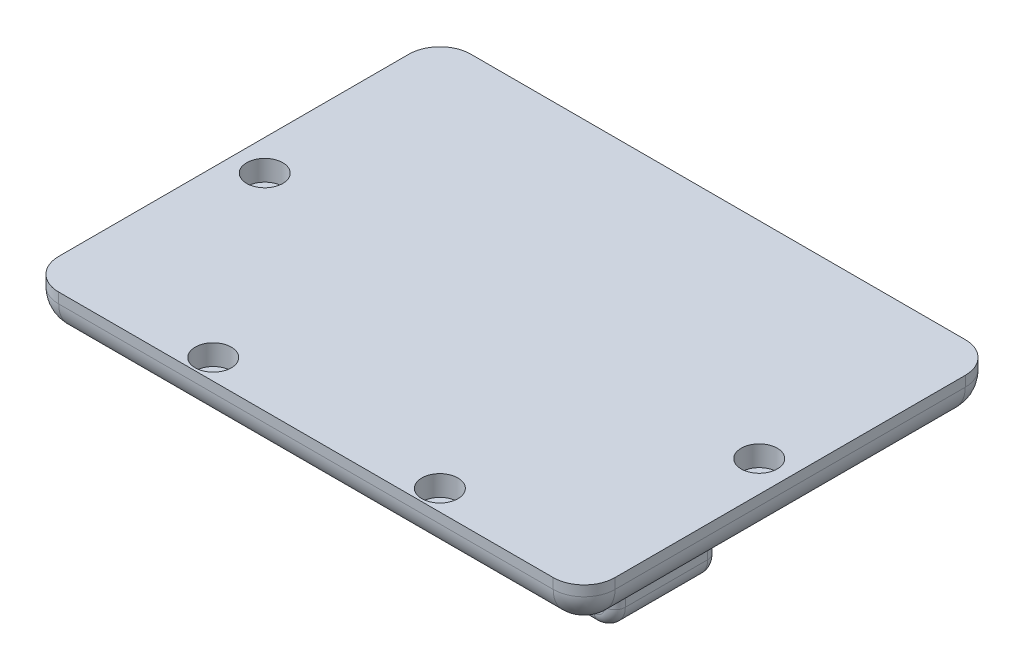
SolidWorks part; units mm, degrees
ref_plane "Plan de face" through (0, 0, 0) normal (0, 0, 1) x (1, 0, 0)
ref_plane "Plan de dessus" through (0, 0, 0) normal (0, 1, 0) x (1, 0, 0)
ref_plane "Plan de droite" through (0, 0, 0) normal (1, 0, 0) x (0, 0, -1)
sketch "Esquisse1" plane through (0, 0, 0) normal (0, 1, 0) x (1, 0, 0)
  line L1 (-27, 20) -> (27, 20)
  line L2 (-27, 20) -> (-27, -20)
  line L3 (-27, -20) -> (27, -20)
  line L4 (27, 20) -> (27, -20)
  line L5 (-27, 20) -> (27, -20) construction
  line L6 (-27, -20) -> (27, 20) construction
  point P0 (0, 0)
  dimension "D1" = 40
  dimension "D2" = 54
extrude "Boss.-Extru.1" add sketch "Esquisse1" along normal blind 4
sketch "Esquisse2" plane through (0, 4, 0) normal (0, 1, 0) x (1, 0, 0)
  line L0 (-27, 20) -> (-27, -20) construction
  line L1 (-27, -20) -> (27, -20) construction
  line L2 (27, -20) -> (27, 20) construction
  circle A0 centre (-24, 0) radius 1.75
  circle A1 centre (-11, -18) radius 1.75
  circle A2 centre (11, -18) radius 1.75
  circle A3 centre (24, 0) radius 1.75
  dimension "D3" = 3.5
  dimension "D6" = 3.5
  dimension "D7" = 3.5
  dimension "D12" = 3.5
  dimension "D1" = 3
  dimension "D2" = 20
  dimension "D4" = 2
  dimension "D5" = 16
  dimension "D8" = 2
  dimension "D9" = 16
  dimension "D10" = 3
  dimension "D11" = 20
fillet "Congé1" radius 3 8 edges at (27, 2, 20) (0, 0, 20) (-27, 2, 20) (-27, 0, 0) (-27, 2, -20) (27, 0, 0) (0, 0, -20) (27, 2, -20)
sketch "Esquisse3" plane through (0, 0, 0) normal (0, -1, 0) x (1, 0, 0)
  line L1 (15, -5) -> (-15, -5)
  line L2 (15, -5) -> (15, 5)
  line L3 (15, 5) -> (-15, 5)
  line L4 (-15, -5) -> (-15, 5)
  line L5 (15, -5) -> (-15, 5) construction
  line L6 (15, 5) -> (-15, -5) construction
  point P0 (0, 0)
  dimension "D1" = 30
  dimension "D2" = 10
extrude "Boss.-Extru.3" add sketch "Esquisse3" along normal blind 13
fillet "Congé4" radius 2 4 edges at (-15, 0, 0) (0, 0, 5) (15, 0, 0) (0, 0, -5)
sketch "Esquisse4" plane through (0, 0, -5) normal (0, 0, -1) x (-1, 0, 0)
  line L0 (-15, -13) -> (-15, -2) construction
  line L1 (-12, -4) -> (12, -4)
  line L2 (-12, -4) -> (-12, -10)
  line L3 (-12, -10) -> (12, -10)
  line L4 (12, -4) -> (12, -10)
  line L5 (-12, -4) -> (12, -10) construction
  line L6 (-12, -10) -> (12, -4) construction
  line L9 (15, -13) -> (-15, -13) construction
  line L10 (15, -2) -> (-15, -2) construction
  point P0 (0, -7)
  dimension "D1" = 24
  dimension "D2" = 3
  dimension "D3" = 3
  dimension "D4" = 2
extrude "Enlèv. mat.-Extru.1" cut sketch "Esquisse4" against normal blind 8
fillet "Congé15" radius 1 18 edges at (-12, -7, -5) (0, -10, -5) (12, -7, -5) (0, -4, -5) (15.5858, -0.5858, -5.5858) (-15.5858, -0.5858, -5.5858) (-15.5858, -0.5858, 5.5858) (15.5858, -0.5858, 5.5858) (15, -7.5, -5) (0, -13, -5) (-15, -7.5, -5) (-15, -7.5, 5) (15, -7.5, 5) (0, -13, 5) (-12, -4, -1) (-12, -10, -1) (12, -10, -1) (12, -4, -1)
fillet "Congé16" radius 2 6 edges at (-14.7071, -12.7071, -4.7071) (-14.7071, -12.7071, 4.7071) (14.7071, -12.7071, 4.7071) (14.7071, -12.7071, -4.7071) (15, -13, 0) (-15, -13, 0)
extrude "Enlèv. mat.-Extru.2" cut sketch "Esquisse2" against normal blind 2
